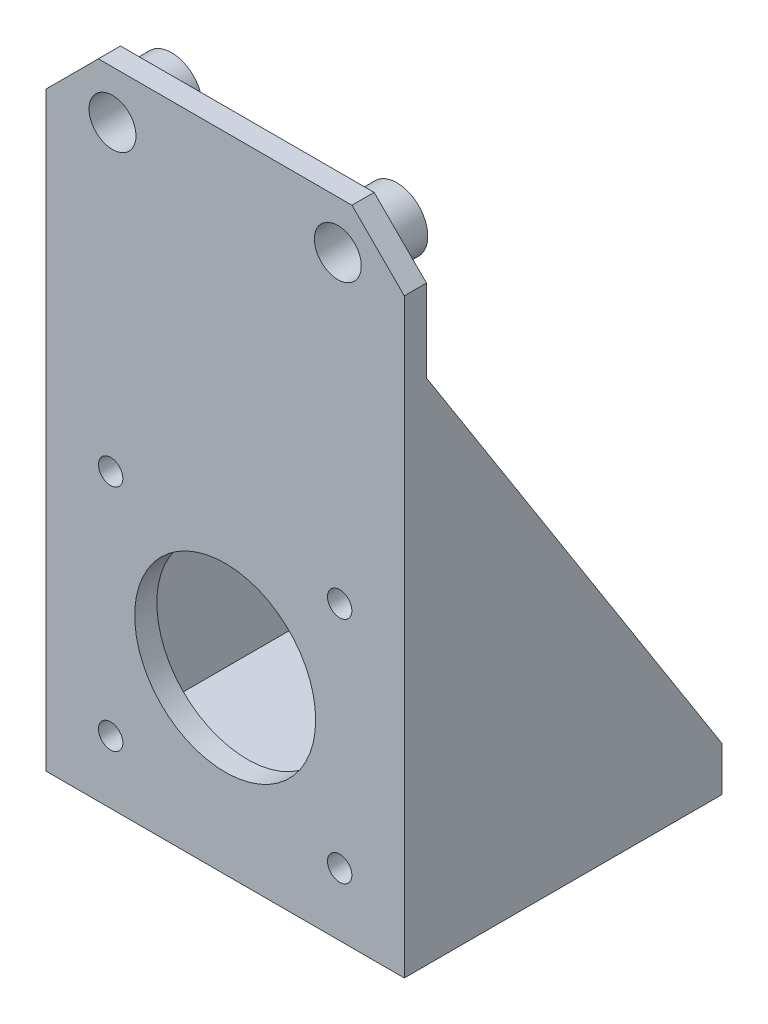
SolidWorks part; units mm, degrees
ref_plane "Front Plane" through (0, 0, 0) normal (0, 0, 1) x (1, 0, 0)
ref_plane "Top Plane" through (0, 0, 0) normal (0, 1, 0) x (1, 0, 0)
ref_plane "Right Plane" through (0, 0, 0) normal (1, 0, 0) x (0, 0, -1)
sketch "Sketch1" plane through (0, 0, 0) normal (0, 0, 1) x (1, 0, 0)
  line L0 (-33.8223, -6) -> (-33.8223, 36.5)
  line L2 (8.6777, 36.5) -> (8.6777, -6)
  line L3 (8.6777, -6) -> (-33.8223, -6)
  line L5 (-33.8223, 36.5) -> (8.6777, 36.5) construction
  line L7 (-28.8223, 77.55) -> (3.6777, 77.55)
  line L10 (-33.8223, 36.5) -> (-33.8223, 72.55)
  line L11 (-33.8223, 72.55) -> (-28.8223, 77.55)
  line L12 (-12.5723, 36.5) -> (-12.5723, 77.55) construction
  line L13 (8.6777, 36.5) -> (8.6777, 72.55)
  line L14 (8.6777, 72.55) -> (3.6777, 77.55)
  line L15 (-12.5723, 36.5) -> (-12.5723, -6) construction
  line L16 (-33.8223, 15.25) -> (8.6777, 15.25) construction
  line L17 (-28.0723, 30.5) -> (2.9277, 30.5) construction
  line L18 (2.9277, 30.5) -> (2.9277, -0.5) construction
  line L19 (2.9277, -0.5) -> (-28.0723, -0.5) construction
  line L20 (-28.0723, 30.5) -> (-28.0723, -0.5) construction
  circle A0 centre (2.9277, 30.5) radius 1.65
  circle A1 centre (2.9277, -0.5) radius 1.65
  circle A2 centre (-28.0723, -0.5) radius 1.65
  circle A3 centre (-28.0723, 30.5) radius 1.65
  circle A4 centre (-12.5723, 15.25) radius 12.25
  circle A5 centre (-27.8223, 71.55) radius 3.175
  circle A6 centre (2.6777, 71.55) radius 3.175
  dimension "D5" = 24.5
  dimension "D10" = 3.3
  dimension "D13" = 6
  dimension "D16" = 6.35
  dimension "D17" = 31
  dimension "D11" = 5.5
  dimension "D14" = 3.3
  dimension "D1" = 42.5
  dimension "D2" = 42.5
  dimension "D3" = 21.25
  dimension "D4" = 6
  dimension "D6" = 62.3
  dimension "D7" = 21.25
  dimension "D8" = 21.25
  dimension "D9" = 5
  dimension "D12" = 5.5
  dimension "D15" = 6
extrude "Boss-Extrude1" add sketch "Sketch1" along normal blind 3
sketch "Sketch2" plane through (0, 0, 0) normal (0, 0, -1) x (-1, 0, 0)
  circle A0 centre (-2.6777, 71.55) radius 3.175
  circle A1 centre (27.8223, 71.55) radius 3.175
  circle A2 centre (-2.6777, 71.55) radius 4.175
  circle A3 centre (27.8223, 71.55) radius 4.175
  dimension "D1" = 6.35
  dimension "D2" = 6.35
  dimension "D3" = 1
  dimension "D4" = 1
extrude "Boss-Extrude2" add sketch "Sketch2" along normal blind 3
sketch "Sketch3" plane through (0, 0, -3) normal (0, 0, -1) x (-1, 0, 0)
  circle A0 centre (-2.6777, 71.55) radius 4.175
  circle A1 centre (27.8223, 71.55) radius 4.175
  dimension "D1" = 8.35
  dimension "D2" = 8.35
extrude "Boss-Extrude3" add sketch "Sketch3" along normal blind 2
sketch "Sketch4" plane through (0, 0, 0) normal (0, 0, -1) x (-1, 0, 0)
  line L0 (33.8223, -6) -> (-8.6777, -6)
  line L2 (-9.0787, -9) -> (33.4213, -9)
  line L4 (-8.6777, -3) -> (-11.6777, -3)
  line L5 (-8.6777, -6) -> (-8.6777, 72.55) construction
  line L6 (-11.6777, -3) -> (-11.6777, -9)
  line L7 (-11.6777, -9) -> (-9.0787, -9)
  line L8 (-8.6777, -6) -> (-8.6777, -3)
  line L10 (36.8223, -9) -> (33.4213, -9)
  line L11 (36.8223, -3) -> (36.8223, -9)
  line L12 (33.8223, -3) -> (36.8223, -3)
  line L13 (33.8223, -6) -> (33.8223, -3)
  dimension "D1" = 3
  dimension "D2" = 3
  dimension "D4" = 3
extrude "Boss-Extrude4" add sketch "Sketch4" along normal blind 40 and the other way blind 3 separate body
sketch "Sketch5" plane through (0, 0, 3) normal (0, 0, 1) x (1, 0, 0)
  line L1 (8.6777, 48.0314) -> (8.6777, 43.0314)
  line L2 (8.6777, -6) -> (8.6777, 72.55) construction
  line L3 (8.6777, 48.0314) -> (11.6777, 48.0314)
  line L4 (11.6777, 48.0314) -> (11.6777, 43.0314)
  line L5 (11.6777, 43.0314) -> (8.6777, 43.0314)
  line L6 (-33.8223, 45.5314) -> (8.6777, 45.5314) construction
  line L11 (-12.5723, 45.5314) -> (-12.5723, 51.3356) construction
  line L12 (-36.8223, 48.0314) -> (-36.8223, 43.0314)
  line L16 (-33.8223, 48.0314) -> (-36.8223, 48.0314)
  line L17 (-33.8223, 48.0314) -> (-33.8223, 43.0314)
  line L18 (-36.8223, 43.0314) -> (-33.8223, 43.0314)
  circle A0 centre (2.9277, 30.5) radius 1.65 construction
  dimension "D2" = 12.5314
  dimension "D1" = 3
  dimension "D3" = 3
  dimension "D4" = 5
  dimension "D5" = 3
  dimension "D6" = 42.5
extrude "Boss-Extrude5" add sketch "Sketch5" against normal blind 3
sketch "Sketch6" plane through (8.6777, 0, 0) normal (1, 0, 0) x (0, 0, -1)
  line L0 (0, 48.0314) -> (40, -3)
  line L1 (0, 43.0314) -> (36.0808, -3)
  line L2 (0, 48.0314) -> (0, 43.0314)
  line L3 (36.0808, -3) -> (40, -3)
  line L4 (-3, -3) -> (40, -3) construction
extrude "Boss-Extrude7" add sketch "Sketch6" along normal blind 3
sketch "Sketch8" plane through (-36.8223, 0, 0) normal (-1, 0, 0) x (0, 0, 1)
  line L0 (0, 48.0314) -> (0, 43.0314)
  line L1 (0, 43.0314) -> (-36.0808, -3)
  line L2 (-36.0808, -3) -> (-40, -3)
  line L3 (-40, -3) -> (0, 48.0314)
extrude "Boss-Extrude9" add sketch "Sketch8" against normal blind 3
sketch "Sketch9" plane through (0, 0, 3) normal (0, 0, 1) x (1, 0, 0)
  line L0 (-12.5723, 77.55) -> (-12.5723, -9) construction
  line L1 (3.6777, 77.55) -> (-28.8223, 77.55) construction
  line L2 (11.6777, -9) -> (-36.8223, -9) construction
  line L3 (-33.8223, 72.55) -> (-33.8223, -3)
  line L4 (-33.8223, -3) -> (-36.8223, -3)
  line L5 (-36.8223, -3) -> (-36.8223, 72.55)
  line L6 (-36.8223, 72.55) -> (-33.8223, 72.55)
  line L7 (11.6777, -3) -> (11.6777, 72.55)
  line L8 (8.6777, -3) -> (11.6777, -3)
  line L9 (8.6777, 72.55) -> (8.6777, -3)
  line L10 (11.6777, 72.55) -> (8.6777, 72.55)
extrude "Boss-Extrude10" add sketch "Sketch9" against normal blind 3
chamfer "Chamfer1" distance 3 angle 45 2 edges at (11.6777, 72.55, 1.5) (-36.8223, 72.55, 1.5)
sketch "Sketch10" plane through (11.6777, 0, 0) normal (1, 0, 0) x (0, 0, -1)
  line L0 (-3, 64.55) -> (-3, -9)
  line L1 (-3, 69.55) -> (-3, -9) construction
  line L2 (-3, -9) -> (40, -9)
  line L3 (40, -9) -> (40, -3)
  line L4 (40, -3) -> (40, -9) construction
  line L5 (40, -3) -> (-3, 64.55)
extrude "Boss-Extrude12" add sketch "Sketch10" against normal blind 3
sketch "Sketch11" plane through (-36.8223, 0, 0) normal (-1, 0, 0) x (0, 0, 1)
  line L0 (3, -9) -> (3, 64.55)
  line L1 (3, -9) -> (3, 69.55) construction
  line L2 (3, 64.55) -> (-40, -3)
  line L3 (-40, -3) -> (-40, -9)
  line L4 (-40, -9) -> (3, -9)
extrude "Boss-Extrude13" add sketch "Sketch11" against normal blind 3
sketch "Sketch12" plane through (0, 0, 3) normal (0, 0, 1) x (1, 0, 0)
  line L0 (-36.8223, 69.55) -> (-36.8223, 70.9642)
  line L1 (-36.8223, 70.9642) -> (-29.7365, 78.05)
  line L2 (-29.7365, 78.05) -> (4.5919, 78.05)
  line L3 (-12.5723, 78.05) -> (-12.5723, 77.55)
  line L4 (3.6777, 77.55) -> (-28.8223, 77.55) construction
  line L5 (3.6777, 77.55) -> (-28.8223, 77.55)
  line L6 (-28.8223, 77.55) -> (-36.8223, 69.55)
  line L7 (-12.5723, 77.55) -> (-12.5723, 92.983) construction
  line L8 (11.6777, 70.9642) -> (4.5919, 78.05)
  line L9 (11.6777, 69.55) -> (11.6777, 70.9642)
  line L10 (3.6777, 77.55) -> (11.6777, 69.55)
  line M8 (-33.8223, 72.55) -> (-36.8223, 69.55)
  line M12 (11.6777, 69.55) -> (8.6777, 72.55)
  line M13 (8.6777, 72.55) -> (3.6777, 77.55)
  line M14 (3.6777, 77.55) -> (-28.8223, 77.55)
  line M15 (-28.8223, 77.55) -> (-33.8223, 72.55)
  dimension "D1" = 1
  dimension "D2" = 0.5
extrude "Boss-Extrude14" add sketch "Sketch12" against normal blind 3 contours L3 L2 L1 L0 M8 M15 M14 | L9 L8 L2 L3 M12 M14 M13 region at (-36.5653, 70.2571, 3) region at (-3.9902, 77.793, 3)
